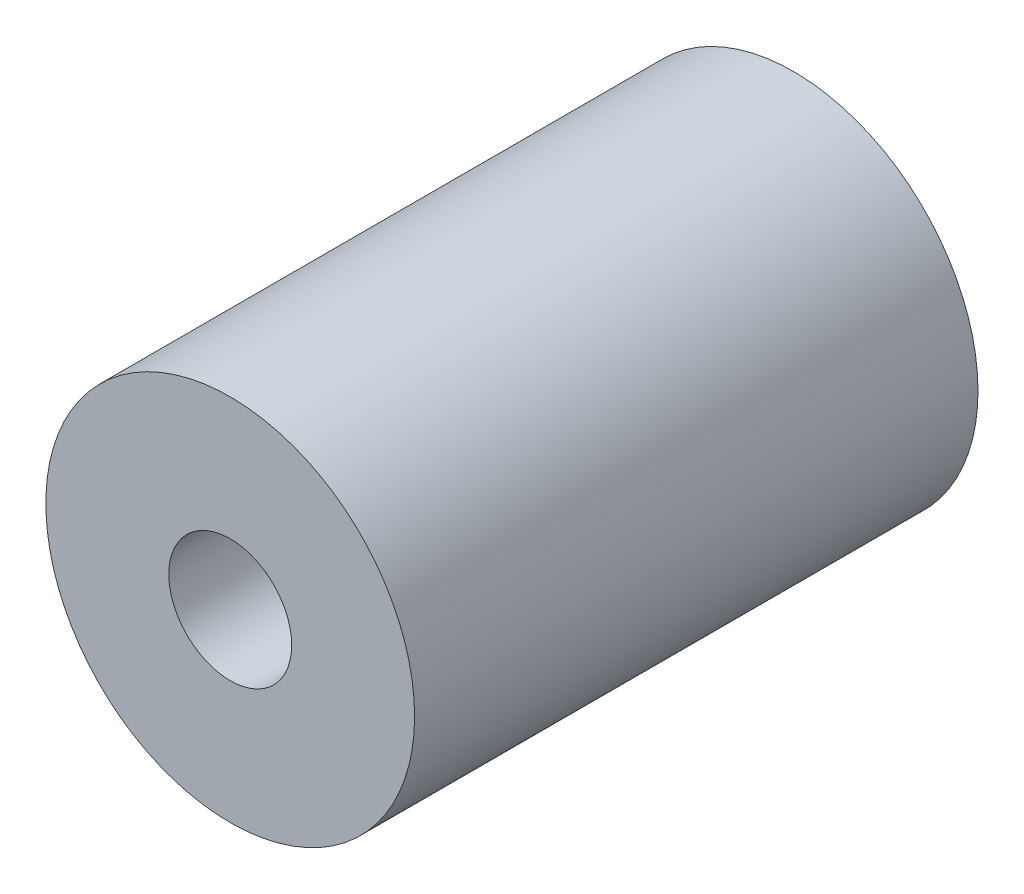
SolidWorks part; units mm, degrees
ref_plane "Спереди" through (0, 0, 0) normal (0, 0, 1) x (1, 0, 0)
ref_plane "Сверху" through (0, 0, 0) normal (0, 1, 0) x (1, 0, 0)
ref_plane "Справа" through (0, 0, 0) normal (1, 0, 0) x (0, 0, -1)
sketch "Эскиз1" plane through (0, 0, 0) normal (0, 0, 1) x (1, 0, 0)
  circle A0 centre (0, 0) radius 3
  circle A1 centre (0, 0) radius 9
  dimension "D1" = 6
  dimension "D2" = 6
extrude "Бобышка-Вытянуть1" add sketch "Эскиз1" along normal blind 27.5
ref_axis "Ось1" through (0, 0, 27.5) along (0, 0, -1)
